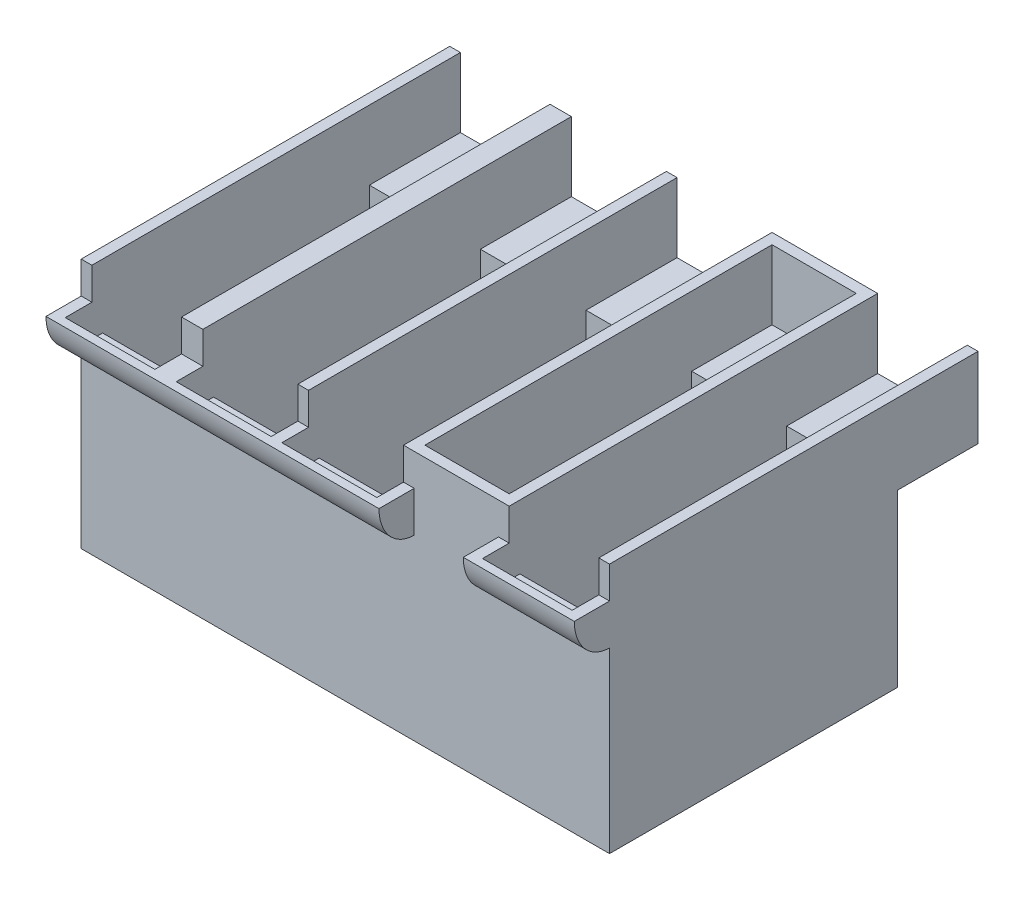
SolidWorks part; units mm, degrees
ref_plane "Front Plane" through (0, 0, 0) normal (0, 0, 1) x (1, 0, 0)
ref_plane "Top Plane" through (0, 0, 0) normal (0, 1, 0) x (1, 0, 0)
ref_plane "Right Plane" through (0, 0, 0) normal (1, 0, 0) x (0, 0, -1)
sketch "Sketch1" plane through (0, 0, 0) normal (0, 1, 0) x (1, 0, 0)
  line L5 (-49.5, 27) -> (49.5, 27)
  line L6 (-49.5, 27) -> (-49.5, -27)
  line L7 (-49.5, -27) -> (49.5, -27)
  line L8 (49.5, 27) -> (49.5, -27)
  line L9 (-49.5, 27) -> (49.5, -27) construction
  line L10 (-49.5, -27) -> (49.5, 27) construction
  point P4 (0, 0)
  dimension "D1" = 99
  dimension "D2" = 54
extrude "Boss-Extrude1" add sketch "Sketch1" along normal blind 2
sketch "Sketch2" plane through (0, 2, 0) normal (0, 1, 0) x (1, 0, 0)
  line L1 (-27.7, -27) -> (-49.5, -27) construction
  line L2 (-49.5, 27) -> (-49.5, -27) construction
  line L3 (-27.7, 12) -> (-27.7, -27) construction
  line L4 (-27.7, -7.5) -> (-7.9, -7.5) construction
  line L6 (-29.7, 12) -> (-29.7, -27) construction
  line L7 (-49.5, -27) -> (49.5, -27) construction
  line L8 (-29.7, -27) -> (-7.9, -27) construction
  line L9 (-7.9, -27) -> (-7.9, 12) construction
  line L11 (11.9, -27) -> (11.9, 12) construction
  line L12 (-49.5, 12) -> (49.5, 12) construction
  line L13 (29.7, -27) -> (29.7, 12) construction
  line L14 (-49.5, -27) -> (-49.5, 12) construction
  line L15 (49.5, -27) -> (49.5, 27) construction
  line L16 (-49.5, -7.5) -> (-29.7, -7.5) construction
  line L18 (-7.9, -7.5) -> (11.9, -7.5) construction
  line L19 (11.9, -7.5) -> (29.7, -7.5) construction
  line L20 (29.7, -7.5) -> (49.5, -7.5) construction
  circle A0 centre (-39.6, -7.5) radius 6.15
  circle A1 centre (-17.8, -7.5) radius 6.15
  circle A2 centre (2, -7.5) radius 6.15
  circle A3 centre (39.6, -7.5) radius 6.15
  point P3 (-82.9639, 18.4485)
  point P4 (-49.5, -5)
  point P8 (0, 0)
  point P18 (0, 0)
  point P19 (-17.8, -7.5)
  point P27 (2, -7.5)
  point P39 (39.6, -7.5)
  point P40 (-29.7, -7.5)
  point P43 (-39.6, -7.5)
  dimension "D2" = 12.3
  dimension "D1" = 2
  dimension "D3" = 15
sketch "Sketch3" plane through (0, 2, -2) normal (0, -1, 0) x (1, 0, 0)
  circle A2 centre (-39.6, 9.5) radius 6.15
  circle A3 centre (-39.6, 9.5) radius 6.15
  circle A6 centre (39.6, 9.5) radius 6.15
  circle A7 centre (39.6, 9.5) radius 6.15
  circle A10 centre (2, 9.5) radius 6.15
  circle A11 centre (2, 9.5) radius 6.15
  circle A13 centre (-17.8, 9.5) radius 6.15
  circle A14 centre (-17.8, 9.5) radius 6.15
  dimension "D2" = 0
  dimension "D1" = 0
  dimension "D3" = 0
  dimension "D4" = 0
extrude "Cut-Extrude1" cut sketch "Sketch3" along normal up to surface (2 mm away) up to face at (0, 0, 0)
sketch "Sketch4" plane through (0, 2, 0) normal (0, 1, 0) x (1, 0, 0)
  line L1 (-49.5, 27) -> (49.5, 27)
  line L2 (-49.5, 27) -> (-49.5, -27)
  line L3 (-49.5, -27) -> (49.5, -27)
  line L4 (49.5, 27) -> (49.5, -27)
extrude "Extrude-Thin1" add sketch "Sketch4" along normal blind 45 thin thin type one direction reverse wall 2
sketch "Sketch5" plane through (0, 2, 0) normal (0, 1, 0) x (1, 0, 0)
  line L0 (-33.45, 0) -> (-30.7, 0) construction
  line L6 (-26.7, 0) -> (-23.95, 0) construction
  line L11 (-11.65, 0) -> (-8.9, 0) construction
  line L12 (8.15, 0) -> (10.9, 0) construction
  line L21 (33.45, 0) -> (30.7, 0) construction
  line L48 (-30.7, 25) -> (-26.7, 25)
  line L50 (-30.7, 25) -> (-30.7, -25)
  line L51 (-30.7, -25) -> (-26.7, -25)
  line L52 (-26.7, 25) -> (-26.7, -25)
  line L55 (-8.9, 25) -> (-6.9, 25)
  line L56 (-8.9, 25) -> (-8.9, -25)
  line L57 (-8.9, -25) -> (-6.9, -25)
  line L58 (-6.9, 25) -> (-6.9, -25)
  line L59 (10.9, 25) -> (12.9, 25)
  line L60 (10.9, 25) -> (10.9, -25)
  line L61 (10.9, -25) -> (12.9, -25)
  line L62 (12.9, 25) -> (12.9, -25)
  line L64 (28.7, 25) -> (30.7, 25)
  line L65 (28.7, 25) -> (28.7, -25)
  line L66 (28.7, -25) -> (30.7, -25)
  line L67 (30.7, 25) -> (30.7, -25)
  point P40 (0, 0)
  point P41 (-108.778, 25.9404)
extrude "Boss-Extrude2" add sketch "Sketch5" along normal up to surface (45 mm away) up to face at (0, 47, 0)
sketch "Sketch6" plane through (0, 47, 0) normal (0, 1, 0) x (1, 0, 0)
  line L0 (-49.5, 27) -> (-49.5, 42.0565)
  line L1 (-49.5, 42.0565) -> (49.5, 42.0565)
  line L2 (49.5, 42.0565) -> (49.5, 27)
  line L3 (-47.5, 40.0565) -> (-47.5, 27)
  line L4 (-47.5, 40.0565) -> (47.5, 40.0565)
  line L5 (47.5, 40.0565) -> (47.5, 27)
  line L8 (-49.5, 27) -> (-49.5, 25)
  line L10 (-49.5, 25) -> (49.5, 25)
  line L11 (49.5, -27) -> (49.5, 27) construction
  line L12 (49.5, 25) -> (49.5, 27)
  line L13 (-47.5, 27) -> (47.5, 27)
  line L14 (-30.7, 25) -> (-47.5, 25) construction
  dimension "D1" = 2
  dimension "D2" = 2
  dimension "D3" = 2
extrude "Boss-Extrude3" add sketch "Sketch6" against normal blind 13
sketch "Sketch7" plane through (0, 34, 0) normal (0, -1, 0) x (1, 0, 0)
  line L1 (-49.5, -42.0565) -> (49.5, -42.0565)
  line L2 (-49.5, -42.0565) -> (-49.5, -27)
  line L3 (-49.5, -27) -> (49.5, -27)
  line L4 (49.5, -42.0565) -> (49.5, -27)
extrude "Boss-Extrude4" add sketch "Sketch7" along normal blind 2
sketch "Sketch8" plane through (0, 47, 0) normal (0, 1, 0) x (1, 0, 0)
  line L0 (-47.5, 25) -> (-47.5, 27)
  line L1 (-47.5, 27) -> (-30.7, 27)
  line L2 (47.5, 27) -> (-47.5, 27) construction
  line L3 (-30.7, 27) -> (-30.7, 25)
  line L4 (-30.7, 25) -> (-47.5, 25)
  line L7 (47.5, 27) -> (-47.5, 27) construction
  line L20 (30.7, 25) -> (47.5, 25)
  line L21 (47.5, 25) -> (47.5, 27)
  line L22 (47.5, 27) -> (30.7, 27)
  line L23 (30.7, 27) -> (30.7, 25)
  line L24 (-8.9, 25) -> (-26.7, 25) construction
  line L25 (-26.7, 27) -> (-8.9, 27)
  line L26 (-26.7, 27) -> (-26.7, 25)
  line L27 (-26.7, 25) -> (-8.9, 25)
  line L28 (-8.9, 27) -> (-8.9, 25)
  line L29 (-8.9, 25) -> (-26.7, 25) construction
  line L31 (-6.9, 25) -> (10.9, 25)
  line L32 (-6.9, 25) -> (-6.9, 27)
  line L33 (-6.9, 27) -> (10.9, 27)
  line L34 (10.9, 25) -> (10.9, 27)
  line L35 (12.9, 25) -> (28.7, 25)
  line L36 (12.9, 25) -> (12.9, 27)
  line L37 (12.9, 27) -> (28.7, 27)
  line L38 (28.7, 25) -> (28.7, 27)
extrude "Cut-Extrude2" cut sketch "Sketch8" against normal up to surface (13 mm away) up to face at (0, 34, -33.5282)
sketch "Sketch9" plane through (0, 47, 0) normal (0, 1, 0) x (1, 0, 0)
  line L22 (47.5, 40.0565) -> (-47.5, 40.0565) construction
  line L23 (-30.7, 27) -> (-26.7, 27)
  line L24 (-30.7, 27) -> (-30.7, 40.0565)
  line L25 (-30.7, 40.0565) -> (-26.7, 40.0565)
  line L26 (-26.7, 27) -> (-26.7, 40.0565)
  line L27 (47.5, 40.0565) -> (-47.5, 40.0565) construction
  line L28 (-8.9, 27) -> (-6.9, 27)
  line L29 (-8.9, 27) -> (-8.9, 40.0565)
  line L30 (-8.9, 40.0565) -> (-6.9, 40.0565)
  line L31 (-6.9, 27) -> (-6.9, 40.0565)
  line L32 (10.9, 27) -> (12.9, 27)
  line L33 (10.9, 27) -> (10.9, 40.0565)
  line L34 (10.9, 40.0565) -> (12.9, 40.0565)
  line L35 (12.9, 27) -> (12.9, 40.0565)
  line L37 (28.7, 27) -> (30.7, 27)
  line L38 (28.7, 27) -> (28.7, 40.0565)
  line L39 (28.7, 40.0565) -> (30.7, 40.0565)
  line L40 (30.7, 27) -> (30.7, 40.0565)
  point P24 (0, 0)
  point P25 (0, 0)
  point P26 (0, 0)
  point P27 (0, 0)
extrude "Boss-Extrude5" add sketch "Sketch9" against normal up to surface (13 mm away) up to face at (1, 34, -27.3056)
sketch "Sketch12" plane through (0, 0, -42.0565) normal (0, 0, -1) x (-1, 0, 0)
  line L104 (-47.5, 47) -> (-30.7, 47) construction
  line L105 (-30.7, 47) -> (-30.7, 34) construction
  line L106 (-30.7, 34) -> (-47.5, 34) construction
  line L107 (-47.5, 34) -> (-47.5, 47) construction
  line L108 (-10.9, 47) -> (6.9, 47) construction
  line L109 (6.9, 47) -> (6.9, 34) construction
  line L110 (6.9, 34) -> (-10.9, 34) construction
  line L111 (-10.9, 34) -> (-10.9, 47) construction
  line L112 (8.9, 47) -> (26.7, 47) construction
  line L113 (26.7, 47) -> (26.7, 34) construction
  line L114 (26.7, 34) -> (8.9, 34) construction
  line L115 (8.9, 34) -> (8.9, 47) construction
  line L116 (47.5, 34) -> (30.7, 34) construction
  line L117 (30.7, 34) -> (30.7, 47) construction
  line L118 (30.7, 47) -> (47.5, 47) construction
  line L119 (47.5, 47) -> (47.5, 34) construction
  line L120 (-47.5, 47) -> (-30.7, 47)
  line L121 (-30.7, 47) -> (-30.7, 34)
  line L122 (-30.7, 34) -> (-47.5, 34)
  line L123 (-47.5, 34) -> (-47.5, 47)
  line L124 (-10.9, 47) -> (6.9, 47)
  line L125 (6.9, 47) -> (6.9, 34)
  line L126 (6.9, 34) -> (-10.9, 34)
  line L127 (-10.9, 34) -> (-10.9, 47)
  line L128 (8.9, 47) -> (26.7, 47)
  line L129 (26.7, 47) -> (26.7, 34)
  line L130 (26.7, 34) -> (8.9, 34)
  line L131 (8.9, 34) -> (8.9, 47)
  line L132 (47.5, 34) -> (30.7, 34)
  line L133 (30.7, 34) -> (30.7, 47)
  line L134 (30.7, 47) -> (47.5, 47)
  line L135 (47.5, 47) -> (47.5, 34)
extrude "Cut-Extrude6" cut sketch "Sketch12" along direction (0, 0, -1) on the side against the normal blind 17
sketch "Sketch13" plane through (0, 0, 27) normal (0, 0, 1) x (1, 0, 0)
  line L0 (30.7, 47) -> (47.5, 47) construction
  line L1 (-6.9, 47) -> (10.9, 47) construction
  line L2 (-26.7, 47) -> (-8.9, 47) construction
  line L3 (-47.5, 47) -> (-30.7, 47) construction
  line L4 (30.7, 47) -> (47.5, 47) construction
  line L5 (-6.9, 47) -> (10.9, 47) construction
  line L6 (-26.7, 47) -> (-8.9, 47) construction
  line L7 (-47.5, 47) -> (-30.7, 47) construction
  line L9 (-47.5, 47) -> (-30.7, 47)
  line L10 (-47.5, 47) -> (-47.5, 35)
  line L11 (-47.5, 35) -> (-30.7, 35)
  line L12 (-30.7, 47) -> (-30.7, 35)
  line L13 (-26.7, 47) -> (-8.9, 47)
  line L14 (-26.7, 47) -> (-26.7, 35)
  line L15 (-26.7, 35) -> (-8.9, 35)
  line L16 (-8.9, 47) -> (-8.9, 35)
  line L17 (-6.9, 47) -> (10.9, 47)
  line L18 (-6.9, 47) -> (-6.9, 35)
  line L19 (-6.9, 35) -> (10.9, 35)
  line L20 (10.9, 47) -> (10.9, 35)
  line L21 (30.7, 47) -> (47.5, 47)
  line L22 (30.7, 47) -> (30.7, 35)
  line L23 (30.7, 35) -> (47.5, 35)
  line L24 (47.5, 47) -> (47.5, 35)
  dimension "D1" = 12
extrude "Cut-Extrude7" cut sketch "Sketch13" against normal up to surface (2 mm away) up to face at (-39.1, 24.5, 25)
sketch "Sketch14" plane through (-49.5, 0, 0) normal (-1, 0, 0) x (0, 0, 1)
  line L0 (27, 35) -> (27, 47) construction
  line L1 (27, 35) -> (27, 47) construction
  line L2 (27, 41) -> (32, 41) construction
  line L3 (32, 41) -> (33.6, 41) construction
  line L4 (27, 35) -> (27, 33.4) construction
  line L5 (27, 47) -> (27, 0) construction
  line L6 (32, 41) -> (33.6, 41)
  line L7 (27, 33.4) -> (27, 35)
  ellipse E0 centre (27, 41) end of major axis (27, 47) minor radius 5 (27, 35) -> (32, 41) ccw
  ellipse E1 centre (27, 41) end of major axis (27, 48.6) minor radius 6.6 (27, 33.4) -> (33.6, 41) ccw
  dimension "D1" = 5
  dimension "D2" = 1.6
  dimension "D3" = 1.6
extrude "Boss-Extrude6" add sketch "Sketch14" against normal up to surface (99 mm away) up to face at (49.5, 26.3333, -14.0188)
sketch "Sketch15" plane through (0, 0, 27) normal (0, 0, 1) x (1, 0, 0)
  line L0 (47.5, 47) -> (47.5, 35) construction
  line L2 (49.5, 35) -> (49.5, 47) construction
  line L3 (49.5, 47) -> (47.5, 47) construction
  line L4 (10.9, 47) -> (10.9, 35) construction
  line L6 (30.7, 35) -> (30.7, 47) construction
  line L7 (30.7, 47) -> (10.9, 47) construction
  line L8 (-8.9, 47) -> (-8.9, 35) construction
  line L10 (-6.9, 35) -> (-6.9, 47) construction
  line L11 (-6.9, 47) -> (-8.9, 47) construction
  line L12 (-30.7, 47) -> (-30.7, 35) construction
  line L14 (-26.7, 35) -> (-26.7, 47) construction
  line L15 (-26.7, 47) -> (-30.7, 47) construction
  line L16 (-49.5, 47) -> (-49.5, 35) construction
  line L18 (-47.5, 35) -> (-47.5, 47) construction
  line L19 (-47.5, 47) -> (-49.5, 47) construction
  line L20 (47.5, 47) -> (47.5, 27.9029)
  line L21 (47.5, 27.9029) -> (49.5, 27.9029)
  line L22 (49.5, 27.9029) -> (49.5, 47)
  line L23 (49.5, 47) -> (47.5, 47)
  line L24 (10.9, 47) -> (10.9, 27.0296)
  line L25 (10.9, 27.0296) -> (30.7, 27.0296)
  line L26 (30.7, 27.0296) -> (30.7, 47)
  line L27 (30.7, 47) -> (10.9, 47)
  line L28 (-8.9, 47) -> (-8.9, 28.849)
  line L29 (-8.9, 28.849) -> (-6.9, 28.849)
  line L30 (-6.9, 28.849) -> (-6.9, 47)
  line L31 (-6.9, 47) -> (-8.9, 47)
  line L32 (-30.7, 47) -> (-30.7, 30.2317)
  line L33 (-30.7, 30.2317) -> (-26.7, 30.2317)
  line L34 (-26.7, 30.2317) -> (-26.7, 47)
  line L35 (-26.7, 47) -> (-30.7, 47)
  line L36 (-49.5, 47) -> (-49.5, 29.4312)
  line L37 (-49.5, 29.4312) -> (-47.5, 29.4312)
  line L38 (-47.5, 29.4312) -> (-47.5, 47)
  line L39 (-47.5, 47) -> (-49.5, 47)
extrude "Cut-Extrude8" cut sketch "Sketch15" along normal through all
sketch "Sketch16" plane through (-47.5, 0, 0) normal (-1, 0, 0) x (0, 0, 1)
  line L0 (27, 33.4) -> (27, 41)
  line L1 (27, 41) -> (33.6, 41)
  ellipse E0 centre (27, 41) end of major axis (27, 48.6) minor radius 6.6 (27, 33.4) -> (33.6, 41) ccw construction
  ellipse E1 centre (27, 41) end of major axis (27, 48.6) minor radius 6.6 (27, 33.4) -> (33.6, 41) ccw
extrude "Boss-Extrude7" add sketch "Sketch16" along normal up to surface (2 mm away) up to face at (-49.5, 26.3333, -14.0188)
sketch "Sketch17" plane through (-26.7, 0, 0) normal (-1, 0, 0) x (0, 0, 1)
  line L1 (27, 33.4) -> (27, 41)
  line L15 (-27, 0) -> (27, 0)
  line L27 (27, 0) -> (27, 33.4)
  line L28 (33.6, 41) -> (27, 41)
  line L29 (27, 41) -> (27, 47)
  line L30 (27, 47) -> (-42.0565, 47)
  line L31 (-42.0565, 47) -> (-42.0565, 32)
  line L32 (-42.0565, 32) -> (-27, 32)
  line L33 (-27, 32) -> (-27, 0)
  line L36 (33.6, 41) -> (27, 41)
  ellipse E1 centre (27, 41) end of major axis (27, 48.6) minor radius 6.6 (27, 33.4) -> (33.6, 41) ccw
  ellipse E2 centre (27, 41) end of major axis (27, 48.6) minor radius 6.6 (27, 33.4) -> (33.6, 41) ccw
  dimension "D1" = 0
sketch "Sketch18" plane through (-26.7, 0, 0) normal (-1, 0, 0) x (0, 0, 1)
  line L2 (27, 41) -> (27, 33.4)
  line L3 (33.6, 41) -> (27, 41)
  line L4 (27, 41) -> (27, 33.4)
  line L5 (33.6, 41) -> (27, 41)
  ellipse E1 centre (27, 41) end of major axis (27, 48.6) minor radius 6.6 (27, 33.4) -> (33.6, 41) ccw
  ellipse E2 centre (27, 41) end of major axis (27, 48.6) minor radius 6.6 (27, 33.4) -> (33.6, 41) ccw
  dimension "D1" = 0
extrude "Boss-Extrude9" add sketch "Sketch18" along normal up to surface (4 mm away) up to face at (-30.7, 36.8958, 30.5006)
sketch "Sketch19" plane through (-8.9, 0, 0) normal (1, 0, 0) x (0, 0, -1)
  line L2 (-27, 33.4) -> (-27, 41)
  line L3 (-27, 41) -> (-33.6, 41)
  line L4 (-27, 33.4) -> (-27, 41)
  line L5 (-27, 41) -> (-33.6, 41)
  ellipse E1 centre (-27, 41) end of major axis (-27, 48.6) minor radius 6.6 (-33.6, 41) -> (-27, 33.4) ccw
  ellipse E2 centre (-27, 41) end of major axis (-27, 48.6) minor radius 6.6 (-33.6, 41) -> (-27, 33.4) ccw
  dimension "D1" = 0
extrude "Boss-Extrude10" add sketch "Sketch19" along normal up to surface (2 mm away) up to face at (-6.9, 36.8958, 30.5006)
sketch "Sketch20" plane through (47.5, 0, 0) normal (1, 0, 0) x (0, 0, -1)
  line L2 (-27, 33.4) -> (-27, 41)
  line L3 (-27, 41) -> (-33.6, 41)
  line L4 (-27, 33.4) -> (-27, 41)
  line L5 (-27, 41) -> (-33.6, 41)
  ellipse E1 centre (-27, 41) end of major axis (-27, 48.6) minor radius 6.6 (-33.6, 41) -> (-27, 33.4) ccw
  ellipse E2 centre (-27, 41) end of major axis (-27, 48.6) minor radius 6.6 (-33.6, 41) -> (-27, 33.4) ccw
  dimension "D1" = 0
extrude "Boss-Extrude11" add sketch "Sketch20" along normal up to surface (2 mm away) up to face at (49.5, 26.3333, -14.0188)
sketch "Sketch21" plane through (10.9, 0, 0) normal (1, 0, 0) x (0, 0, -1)
  line L2 (-27, 33.4) -> (-27, 41)
  line L3 (-27, 41) -> (-33.6, 41)
  line L4 (-27, 33.4) -> (-27, 41)
  line L5 (-27, 41) -> (-33.6, 41)
  ellipse E1 centre (-27, 41) end of major axis (-27, 48.6) minor radius 6.6 (-33.6, 41) -> (-27, 33.4) ccw
  ellipse E2 centre (-27, 41) end of major axis (-27, 48.6) minor radius 6.6 (-33.6, 41) -> (-27, 33.4) ccw
  dimension "D1" = 0
extrude "Boss-Extrude12" add sketch "Sketch21" along normal blind 2
sketch "Sketch22" plane through (30.7, 0, 0) normal (-1, 0, 0) x (0, 0, 1)
  line L2 (27, 41) -> (27, 33.4)
  line L3 (33.6, 41) -> (27, 41)
  line L4 (27, 41) -> (27, 33.4)
  line L5 (33.6, 41) -> (27, 41)
  ellipse E1 centre (27, 41) end of major axis (27, 48.6) minor radius 6.6 (27, 33.4) -> (33.6, 41) ccw
  ellipse E2 centre (27, 41) end of major axis (27, 48.6) minor radius 6.6 (27, 33.4) -> (33.6, 41) ccw
  dimension "D1" = 0
extrude "Boss-Extrude13" add sketch "Sketch22" along normal blind 2
sketch "Sketch23" plane through (0, 0, 0) normal (0, -1, 0) x (1, 0, 0)
  line L0 (-45.75, 13.65) -> (-45.75, 27) construction
  line L1 (-49.5, 27) -> (49.5, 27) construction
  line L2 (-45.75, 27) -> (-33.45, 27) construction
  line L3 (-33.45, 27) -> (-33.45, 13.65) construction
  line L4 (-45.75, 13.65) -> (-33.45, 27) construction
  line L5 (-33.45, 27) -> (-45.75, 27) construction
  line L6 (-33.45, 13.65) -> (-45.75, 13.65) construction
  line L7 (-45.75, 27) -> (-33.45, 13.65) construction
  line L8 (-49.5, 17.325) -> (49.5, 17.325) construction
  line L9 (-40.1, 23.325) -> (-39.1, 23.325)
  line L10 (-40.6, 22.825) -> (-40.6, 17.825)
  line L11 (-40.1, 17.325) -> (-39.1, 17.325)
  line L12 (-38.6, 22.825) -> (-38.6, 17.825)
  line L13 (-40.6, 23.325) -> (-38.6, 17.325) construction
  line L14 (-40.6, 17.325) -> (-38.6, 23.325) construction
  line L15 (-49.5, -27) -> (-49.5, 27) construction
  line L16 (49.5, 27) -> (49.5, -27) construction
  line L17 (-17.8, 7.5) -> (-17.8, 27) construction
  line L18 (-39.6, 20.325) -> (39.6, 20.325) construction
  line L19 (2, 7.5) -> (2, 27) construction
  line L20 (12.9, 27) -> (-49.5, 27) construction
  line L21 (-49.5, 23.325) -> (49.5, 23.325) construction
  line L22 (39.6, 7.5) -> (39.6, 27) construction
  line L23 (-18.3, 23.325) -> (-17.3, 23.325)
  line L24 (-18.8, 22.825) -> (-18.8, 17.825)
  line L25 (-18.3, 17.325) -> (-17.3, 17.325)
  line L26 (-16.8, 22.825) -> (-16.8, 17.825)
  line L27 (-18.8, 23.325) -> (-16.8, 17.325) construction
  line L28 (-18.8, 17.325) -> (-16.8, 23.325) construction
  line L29 (1.5, 23.325) -> (2.5, 23.325)
  line L30 (1, 22.825) -> (1, 17.825)
  line L31 (1.5, 17.325) -> (2.5, 17.325)
  line L32 (3, 22.825) -> (3, 17.825)
  line L33 (1, 23.325) -> (3, 17.325) construction
  line L34 (1, 17.325) -> (3, 23.325) construction
  line L35 (39.1, 23.325) -> (40.1, 23.325)
  line L36 (38.6, 22.825) -> (38.6, 17.825)
  line L37 (39.1, 17.325) -> (40.1, 17.325)
  line L38 (40.6, 22.825) -> (40.6, 17.825)
  line L39 (38.6, 23.325) -> (40.6, 17.325) construction
  line L40 (38.6, 17.325) -> (40.6, 23.325) construction
  line L41 (-45.75, -12) -> (-45.75, 1.35) construction
  line L42 (-45.75, 1.35) -> (-33.45, 1.35) construction
  line L43 (-33.45, -12) -> (-45.75, -12) construction
  line L44 (-39.6, 1.35) -> (-39.6, 7.5) construction
  line L45 (-45.75, 1.35) -> (-33.45, -12) construction
  line L46 (-33.45, -12) -> (-33.45, 1.35) construction
  line L47 (-33.45, 1.35) -> (-45.75, -12) construction
  line L48 (-39.6, -5.325) -> (39.6, -5.325) construction
  line L49 (-17.8, 7.5) -> (-17.8, -5.325) construction
  line L50 (39.6, -5.325) -> (39.6, 7.5) construction
  line L51 (2, 7.5) -> (2, -5.325) construction
  circle A0 centre (-39.6, 7.5) radius 6.15 construction
  arc A1 (-40.6, 17.825) -> (-40.1, 17.325) centre (-40.1, 17.825) ccw
  arc A2 (-38.6, 17.825) -> (-39.1, 17.325) centre (-39.1, 17.825) cw
  arc A3 (-39.1, 23.325) -> (-38.6, 22.825) centre (-39.1, 22.825) cw
  arc A4 (-40.1, 23.325) -> (-40.6, 22.825) centre (-40.1, 22.825) ccw
  arc A5 (-18.8, 17.825) -> (-18.3, 17.325) centre (-18.3, 17.825) ccw
  arc A6 (-16.8, 17.825) -> (-17.3, 17.325) centre (-17.3, 17.825) cw
  arc A7 (-17.3, 23.325) -> (-16.8, 22.825) centre (-17.3, 22.825) cw
  arc A8 (-18.3, 23.325) -> (-18.8, 22.825) centre (-18.3, 22.825) ccw
  arc A9 (1, 17.825) -> (1.5, 17.325) centre (1.5, 17.825) ccw
  arc A10 (3, 17.825) -> (2.5, 17.325) centre (2.5, 17.825) cw
  arc A11 (2.5, 23.325) -> (3, 22.825) centre (2.5, 22.825) cw
  arc A12 (1.5, 23.325) -> (1, 22.825) centre (1.5, 22.825) ccw
  arc A13 (38.6, 17.825) -> (39.1, 17.325) centre (39.1, 17.825) ccw
  arc A14 (40.6, 17.825) -> (40.1, 17.325) centre (40.1, 17.825) cw
  arc A15 (40.1, 23.325) -> (40.6, 22.825) centre (40.1, 22.825) cw
  arc A16 (39.1, 23.325) -> (38.6, 22.825) centre (39.1, 22.825) ccw
  circle A17 centre (-39.6, -5.325) radius 3
  circle A18 centre (-39.6, -5.325) radius 2
  circle A19 centre (-17.8, -5.325) radius 3
  circle A20 centre (-17.8, -5.325) radius 2
  circle A21 centre (2, -5.325) radius 3
  circle A22 centre (2, -5.325) radius 2
  circle A23 centre (39.6, -5.325) radius 3
  circle A24 centre (39.6, -5.325) radius 2
  point P8 (-39.6, 20.325)
  point P12 (-39.6, 13.65)
  point P16 (-39.6, 20.325)
  point P64 (-17.8, 20.325)
  point P65 (-17.8, 20.325)
  point P82 (2, 20.325)
  point P83 (2, 20.325)
  point P100 (39.6, 20.325)
  point P109 (-39.6, 1.35)
  point P118 (0, 0)
  dimension "D3" = 0.5
  dimension "D4" = 6
  dimension "D5" = 4
  dimension "D1" = 2
  dimension "D2" = 6
extrude "Cut-Extrude9" cut sketch "Sketch23" against normal blind 0.6
